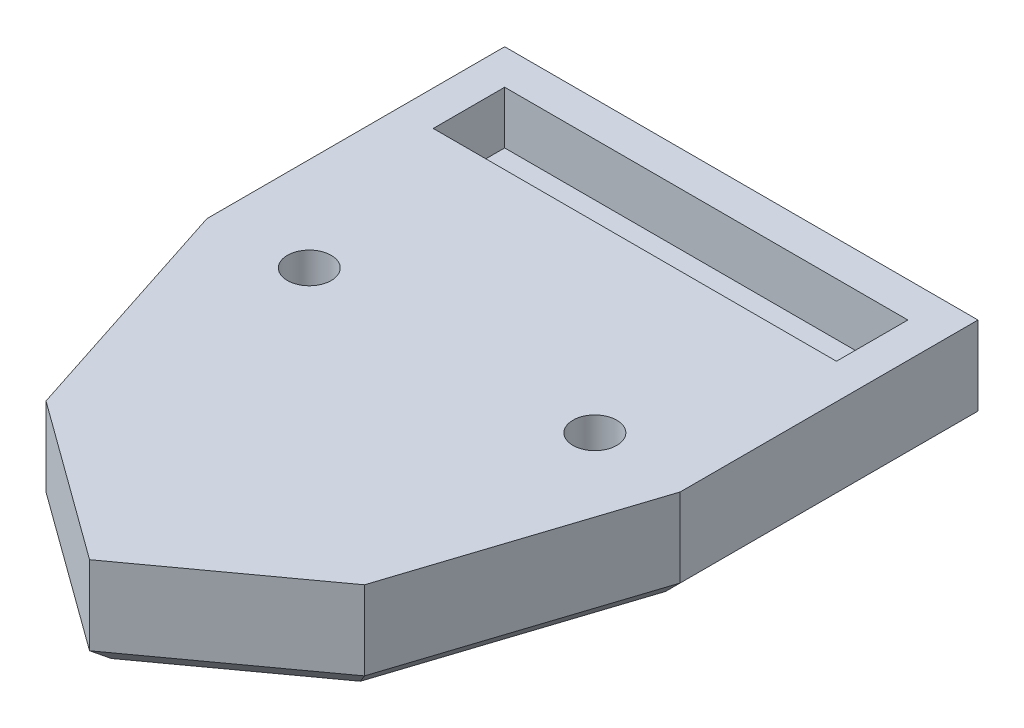
SolidWorks part; units mm, degrees
other "Markup1"
sketch "Sketch10" plane through (13.5, 0, 18.128) normal (0.5841, -0.3918, 0.7108) x (0.6882, 0.7034, -0.1778)
sketch "Sketch11" plane through (13.5, 0, 18.128) normal (0.5841, -0.3918, 0.7108) x (0.6882, 0.7034, -0.1778)
ref_plane "Front Plane" through (0, 0, 0) normal (0, 0, 1) x (1, 0, 0)
ref_plane "Top Plane" through (0, 0, 0) normal (0, 1, 0) x (1, 0, 0)
ref_plane "Right Plane" through (0, 0, 0) normal (1, 0, 0) x (0, 0, -1)
sketch "Sketch1" plane through (0, 0, 0) normal (0, 1, 0) x (1, 0, 0)
  line L1 (-13.5, -14) -> (13.5, -14)
  line L2 (-13.5, -14) -> (-13.5, 14)
  line L3 (-13.5, 14) -> (13.5, 14)
  line L4 (13.5, -14) -> (13.5, 14)
  line L5 (-13.5, -14) -> (13.5, 14) construction
  line L6 (-13.5, 14) -> (13.5, -14) construction
  point P0 (0, 0)
  dimension "D1" = 27
  dimension "D2" = 28
extrude "Boss-Extrude1" add sketch "Sketch1" along normal blind 5.5
sketch "Sketch2" plane through (0, 0, -14) normal (0, 0, 1) x (1, 0, 0)
  line L0 (-11.625, 5.5) -> (-11.625, 7.25)
  line L1 (-11.5, 5.75) -> (11.5, 5.75) construction
  line L2 (-11.5, 5.75) -> (-11.5, 7.25) construction
  line L3 (-11.5, 7.25) -> (11.5, 7.25) construction
  line L4 (11.5, 5.75) -> (11.5, 7.25) construction
  line L5 (-11.5, 5.75) -> (11.5, 7.25) construction
  line L6 (-11.5, 7.25) -> (11.5, 5.75) construction
  line L8 (-10.125, 8.25) -> (-13.125, 8.25)
  line L9 (-13.125, 8.25) -> (-13.125, 5.5)
  line L10 (-11.625, 7.25) -> (-10.125, 7.25)
  line L13 (-13.5, 5.5) -> (13.5, 5.5) construction
  line L17 (0, 0) -> (0, 5.5) construction
  line L23 (-13.125, 5.5) -> (-11.625, 5.5)
  line L24 (13.125, 8.25) -> (13.125, 5.5)
  line L25 (10.125, 8.25) -> (13.125, 8.25)
  line L27 (11.625, 5.5) -> (11.625, 7.25)
  line L28 (13.125, 5.5) -> (11.625, 5.5)
  line L29 (-10.125, 7.25) -> (-10.125, 8.25)
  line L30 (11.625, 7.25) -> (10.125, 7.25)
  line L31 (10.125, 7.25) -> (10.125, 8.25)
  point P0 (0, 6.5)
  dimension "D1" = 23
  dimension "D2" = 1.5
  dimension "D3" = 0.25
  dimension "D4" = 0.125
  dimension "D5" = 1.5
  dimension "D6" = 1
  dimension "D7" = 1.5
extrude "Boss-Extrude3" [suppressed] add sketch "Sketch2" along normal offset from surface (17 mm away) 2
sketch "Sketch4" plane through (0, 0, 0) normal (0, -1, 0) x (1, 0, 0)
  line L2 (-13.5, 14) -> (13.5, 14)
  line L4 (-13.5, 14) -> (-13.5, 29)
  line L7 (13.5, 14) -> (13.5, 29)
  line L8 (-13.5, 29) -> (13.5, 29)
  dimension "D1" = 15
extrude "Boss-Extrude5" add sketch "Sketch4" against normal up to surface (5.5 mm away) up to face at (0, 5.5, 0)
fillet "Fillet2" [suppressed] radius 1
ref_plane "Plane1" through (0, -1.2155, -0.1063) normal (0, 0.9962, 0.0872) x (-1, 0, 0)
sketch "Sketch5" plane through (0, -2.9887, 20.1605) normal (0, -0.9962, -0.0872) x (1, 0, 0)
  line L0 (-2.9896, -22.041) -> (-1.4948, -4.166)
  line L1 (1.4948, -4.166) -> (2.9896, -22.041)
  line L2 (13.5, -34.291) -> (-13.5, -34.291) construction
  circle A0 centre (0, -22.291) radius 3
  circle A1 centre (0, -4.291) radius 1.5
  dimension "D1" = 6
  dimension "D2" = 3
  dimension "D3" = 18
  dimension "D4" = 12
extrude "Cut-Extrude1" cut sketch "Sketch5" against normal blind 4 contours A0 | A1 L0 A0 L1 | A1
fillet "Fillet3" radius 0.6 4 edges at (0, 0, -4.9656) (2.2422, 0, 7.2684) (0, 0, 17.6203) (-2.2422, 0, 7.2684)
sketch "Sketch6" plane through (0, 0, -14) normal (0, 0, -1) x (-1, 0, 0)
  line L1 (-13.5, 0) -> (13.5, 0)
  line L2 (-13.5, 0) -> (-13.5, 10)
  line L3 (-13.5, 10) -> (13.5, 10)
  line L4 (13.5, 0) -> (13.5, 10)
  dimension "D1" = 10
extrude "Boss-Extrude6" [suppressed] add sketch "Sketch6" along normal blind 2
sketch "Sketch7" [suppressed] plane through (0, 5.5, 0) normal (0, 1, 0) x (1, 0, 0)
  line L0 (13.5, 12.5) -> (-13.5, 12.5) construction
  line L1 (-8.5, 12.5) -> (-3.5, 12.5)
  line L2 (-8.5, 12.5) -> (-8.5, -18.4688)
  line L3 (-8.5, -18.4688) -> (-3.5, -18.4688)
  line L4 (-3.5, 12.5) -> (-3.5, -18.4688)
  line L5 (-13.5, 12.5) -> (13.5, 12.5) construction
  line L6 (3.5, 12.5) -> (8.5, 12.5)
  line L7 (3.5, 12.5) -> (3.5, -18.3966)
  line L8 (3.5, -18.3966) -> (8.5, -18.3966)
  line L9 (8.5, 12.5) -> (8.5, -18.3966)
  line L10 (-13.5, 12.5) -> (-13.5, -10.5) construction
  line L11 (13.5, -10.5) -> (13.5, 12.5) construction
  dimension "D1" = 5
  dimension "D2" = 5
  dimension "D3" = 5
  dimension "D4" = 5
extrude "Cut-Extrude2" [suppressed] cut sketch "Sketch7" against normal blind 2.54
sketch "Sketch8" plane through (0, 5.5, 0) normal (0, 1, 0) x (1, 0, 0)
  line L4 (-13.5, -29) -> (13.5, -29)
  line L5 (-13.5, -29) -> (13.5, -29)
  line L9 (13.5, -29) -> (13.5, 14)
  line L17 (13.5, 14) -> (-13.5, 14)
  line L19 (13.5, 14) -> (-13.5, 14)
  line L25 (13.5, -29) -> (13.5, 14)
  line L44 (-13.5, 14) -> (-13.5, -29)
  line L45 (-13.5, 14) -> (-13.5, -29)
  dimension "D1" = 0
extrude "Cut-Extrude3" [suppressed] cut sketch "Sketch8" against normal blind 1
fillet "Fillet4" [suppressed] radius 2
sketch "Sketch9" [suppressed] plane through (0, 0, -14.5) normal (0, 0, -1) x (-1, 0, 0)
  line L0 (-3.8951, 9) -> (3.8951, 9) construction
  line L1 (-3.8951, 9) -> (-3.8951, 12) construction
  line L2 (3.8951, 9) -> (3.8951, 12) construction
  line L3 (-3.8951, 9) -> (3.8951, 9)
  line L4 (-3.8951, 9) -> (-3.8951, 12)
  line L5 (3.8951, 9) -> (3.8951, 12)
  line L6 (-11.5, 7) -> (11.5, 7) construction
  line L7 (-11.5, 7) -> (11.5, 7)
  line L8 (-3.8951, 9) -> (-3.8951, 7)
  line L9 (3.8951, 9) -> (3.8951, 7)
  line L10 (-3.8951, 10) -> (3.8951, 10)
  line L11 (13.5, 10) -> (-13.5, 10) construction
  line M4 (13.5, 10) -> (-13.5, 10)
extrude "Cut-Extrude4" [suppressed] cut sketch "Sketch9" against normal up to surface (2 mm away) contours L9 L3 L8 L7 | L3 L5 L4 M4
chamfer "Chamfer2" [suppressed] distance 0.25 angle 89
chamfer "Chamfer3" [suppressed] distance 0.25 angle 89
sketch "Sketch12" plane through (0, 0, 0) normal (0, -1, 0) x (1, 0, 0)
  circle A0 centre (8.1451, 2.5) radius 1.25
  circle A1 centre (-8.1451, 2.5) radius 1.25
  dimension "D1" = 2.5
  dimension "D2" = 2.5
extrude "Cut-Extrude5" cut sketch "Sketch12" against normal through all
sketch "Sketch13" plane through (0, 5.5, 0) normal (0, 1, 0) x (1, 0, 0)
  line L0 (13.5, 14) -> (-13.5, 14) construction
  line L1 (-11.5, 12) -> (11.5, 12)
  line L2 (-11.5, 12) -> (-11.5, 7.9247)
  line L3 (-11.5, 7.9247) -> (11.5, 7.9247)
  line L4 (11.5, 12) -> (11.5, 7.9247)
  line L5 (-11.5, 12) -> (11.5, 7.9247) construction
  line L6 (-11.5, 7.9247) -> (11.5, 12) construction
  point P0 (0, 9.9623)
  point P5 (0, 9.7123)
  point P9 (0, 0)
  point P10 (0, 0)
  point P11 (0, 10.5872)
  point P12 (0, 9.9623)
  dimension "D1" = 2
  dimension "D2" = 23
  dimension "D3" = 0.25
sketch "Sketch14" plane through (0, 0, 0) normal (0, -1, 0) x (1, 0, 0)
  line L4 (-13.5, 2.9861) -> (-9.0826, 16.5815)
  line L5 (-9.0826, 16.5815) -> (0, 23.1804)
  line L6 (0, 23.1804) -> (9.0826, 16.5815)
  line L7 (9.0826, 16.5815) -> (13.5, 2.9861)
  line L13 (15.875, 5.45) -> (9.0517, 26.45)
  line L14 (9.0517, 26.45) -> (-9.0517, 26.45)
  line L15 (-9.0517, 26.45) -> (-15.875, 5.45)
  line L16 (-15.875, 5.45) -> (-15.875, -14)
  line L17 (-15.875, -14) -> (-13.875, -14)
  line L18 (-13.875, -14) -> (-13.875, 3.45)
  line L19 (-13.875, 3.45) -> (-9.5079, 16.8905)
  line L20 (-9.5079, 16.8905) -> (0, 23.7984)
  line L21 (0, 23.7984) -> (9.5079, 16.8905)
  line L22 (9.5079, 16.8905) -> (13.875, 3.45)
  line L23 (13.875, 3.45) -> (13.875, -14)
  line L24 (13.875, -14) -> (15.875, -14)
  line L25 (15.875, -14) -> (15.875, 5.45)
  line L32 (-13.5, 4.6041) -> (-9.5079, 16.8905) construction
  line L33 (-9.5079, 16.8905) -> (0, 23.7984) construction
  line L34 (0, 23.7984) -> (9.5079, 16.8905) construction
  line L35 (9.5079, 16.8905) -> (13.5, 4.6041) construction
  line L42 (13.5, 29) -> (13.5, -14) construction
  line L43 (-13.5, -14) -> (-13.5, 29) construction
  line L44 (13.5, 29) -> (-13.5, 29) construction
  line L45 (13.5, 29) -> (13.5, 2.9861)
  line L46 (-13.5, 2.9861) -> (-13.5, 29)
  line L47 (13.5, 29) -> (-13.5, 29)
  line L48 (-13.3995, 3.2955) -> (-9.0826, 16.5815) construction
  line L49 (-13.875, 3.45) -> (-9.5079, 16.8905) construction
  line L50 (9.0826, 16.5815) -> (13.3995, 3.2955) construction
  line L51 (9.5079, 16.8905) -> (13.875, 3.45) construction
  point P24 (0, 0)
  point P27 (0, 0)
  dimension "D1" = 0
  dimension "D3" = 0.5
extrude "Cut-Extrude6" cut sketch "Sketch14" against normal through all
extrude "Cut-Extrude7" cut sketch "Sketch13" against normal blind 3 contours L3 L4 L1 L2
sketch "Sketch16" plane through (0, 0, 0) normal (0, -1, 0) x (1, 0, 0)
  circle A0 centre (-8.1451, 2.5) radius 3
  circle A1 centre (8.1451, 2.5) radius 3
  dimension "D1" = 6
extrude "Cut-Extrude8" cut sketch "Sketch16" against normal blind 3
chamfer "Chamfer4" distance 1 6 edges at (13.5, 0, -5.507) (11.2913, 0, 9.7838) (4.5413, 0, 19.8809) (-4.5413, 0, 19.8809) (-11.2913, 0, 9.7838) (-13.5, 0, -5.507)
